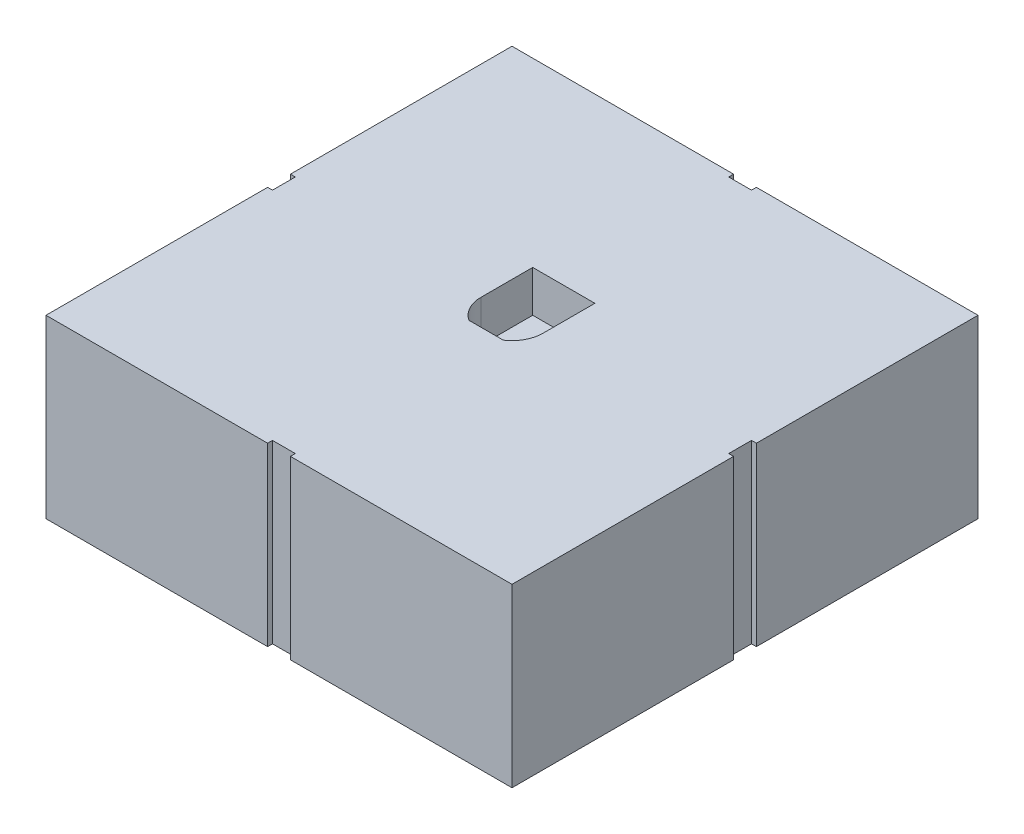
SolidWorks part; units mm, degrees
ref_plane "Front Plane" through (0, 0, 0) normal (0, 0, 1) x (1, 0, 0)
ref_plane "Top Plane" through (0, 0, 0) normal (0, 1, 0) x (1, 0, 0)
ref_plane "Right Plane" through (0, 0, 0) normal (1, 0, 0) x (0, 0, -1)
sketch "Sketch1" plane through (0, 0, 0) normal (0, 1, 0) x (1, 0, 0)
  line L1 (0, 0) -> (142.8, 0)
  line L2 (0, 0) -> (0, 142.8)
  line L3 (0, 142.8) -> (142.8, 142.8)
  line L4 (142.8, 0) -> (142.8, 142.8)
  dimension "D1" = 142.8
  dimension "D2" = 142.8
extrude "Boss-Extrude1" add sketch "Sketch1" along normal blind 54
sketch "Sketch2" plane through (0, 54, 0) normal (0, 1, 0) x (1, 0, 0)
  line L0 (71.4, 142.8) -> (71.4, 0) construction
  line L1 (142.8, 142.8) -> (0, 142.8) construction
  line L2 (0, 0) -> (142.8, 0) construction
  line L3 (0, 71.4) -> (142.8, 71.4) construction
  line L4 (0, 142.8) -> (0, 0) construction
  line L5 (142.8, 0) -> (142.8, 142.8) construction
  line L7 (80.925, 71.4) -> (61.875, 71.4)
  line L8 (80.925, 71.4) -> (80.925, 87.275)
  line L9 (80.925, 87.275) -> (61.875, 87.275)
  line L10 (61.875, 71.4) -> (61.875, 87.275)
  line L11 (66.1349, 79.3375) -> (76.6651, 79.3375)
  line L12 (66.1349, 79.3375) -> (66.1349, 63.4625)
  line L13 (66.1349, 63.4625) -> (76.6651, 63.4625)
  line L14 (76.6651, 79.3375) -> (76.6651, 63.4625)
  line L15 (66.1349, 79.3375) -> (76.6651, 63.4625) construction
  line L16 (66.1349, 63.4625) -> (76.6651, 79.3375) construction
  circle A0 centre (71.4, 71.4) radius 9.525
  point P22 (71.4, 63.4625)
  dimension "D1" = 19.05
  dimension "D2" = 19.05
  dimension "D3" = 7.9375
  dimension "D4" = 23.8125
extrude "Cut-Extrude1" cut sketch "Sketch2" against normal blind 12.7 contours A0 L8 L9 L10 | L7 A0 L14 | L12 A0 L7 | L14 L11 L12 L7 | L11 A0 | L14 A0 L7 | L7 A0 L12 | L14 L7 L12 L13
sketch "Sketch4" plane through (0, 0, 0) normal (0, -1, 0) x (1, 0, 0)
  line L0 (0, -142.8) -> (142.8, 0)
ref_point "Point1"
ref_axis "Axis1" through (71.4, 0, -71.4) along (0, -1, 0)
sketch "Sketch7" plane through (0, 0, 0) normal (0, -1, 0) x (1, 0, 0)
  line L0 (142.8, -142.8) -> (0, -142.8) construction
  line L1 (71.4, -142.8) -> (74.9, -142.8)
  line L3 (71.4, -141.3) -> (74.9, -141.3)
  line L4 (74.9, -142.8) -> (74.9, -141.3)
  line L6 (71.4, -142.8) -> (67.9, -142.8)
  line L8 (71.4, -141.3) -> (67.9, -141.3)
  line L9 (67.9, -142.8) -> (67.9, -141.3)
  dimension "D1" = 3.5
  dimension "D2" = 1.5
  dimension "D3" = 3.5
extrude "Cut-Extrude5" cut sketch "Sketch7" against normal through all
pattern_circular "CirPattern3" count 4 over 360 about axis through (71.4, 0, -71.4) along (0, -1, 0) of "Cut-Extrude5"
